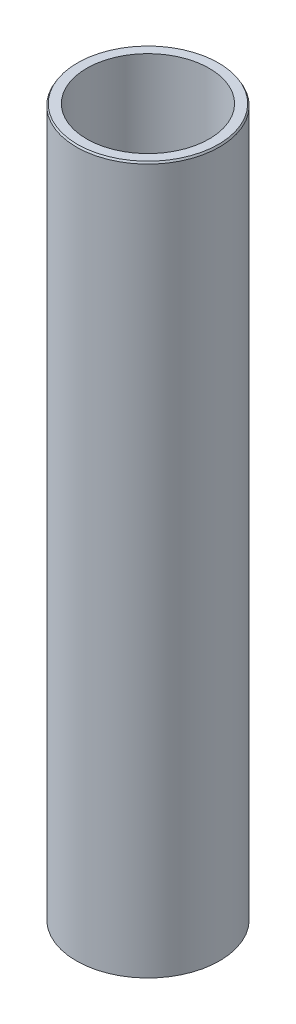
SolidWorks part; units mm, degrees
ref_plane "Front Plane" through (0, 0, 0) normal (0, 0, 1) x (1, 0, 0)
ref_plane "Top Plane" through (0, 0, 0) normal (0, 1, 0) x (1, 0, 0)
ref_plane "Right Plane" through (0, 0, 0) normal (1, 0, 0) x (0, 0, -1)
sketch "Sketch1" plane through (0, 0, 0) normal (0, 1, 0) x (1, 0, 0)
  circle A0 centre (0, 0) radius 52.5
  dimension "SHAFT_OD" = 105
extrude "Boss-Extrude1" add sketch "Sketch1" along normal blind 518.8753
sketch "Sketch2" plane through (0, 0, 0) normal (0, 1, 0) x (1, 0, 0)
  circle A0 centre (0, 0) radius 44.9208
  dimension "BORE_D" = 89.8416
extrude "Cut-Extrude1" cut sketch "Sketch2" along normal through all
chamfer "Chamfer1" distance 1.3231 angle 30 2 edges at (0, 518.8753, 52.5) (0, 0, 52.5) first distance on face at (0, 518.8753, 52.5) first distance on face at (0, 0, 44.9208)
